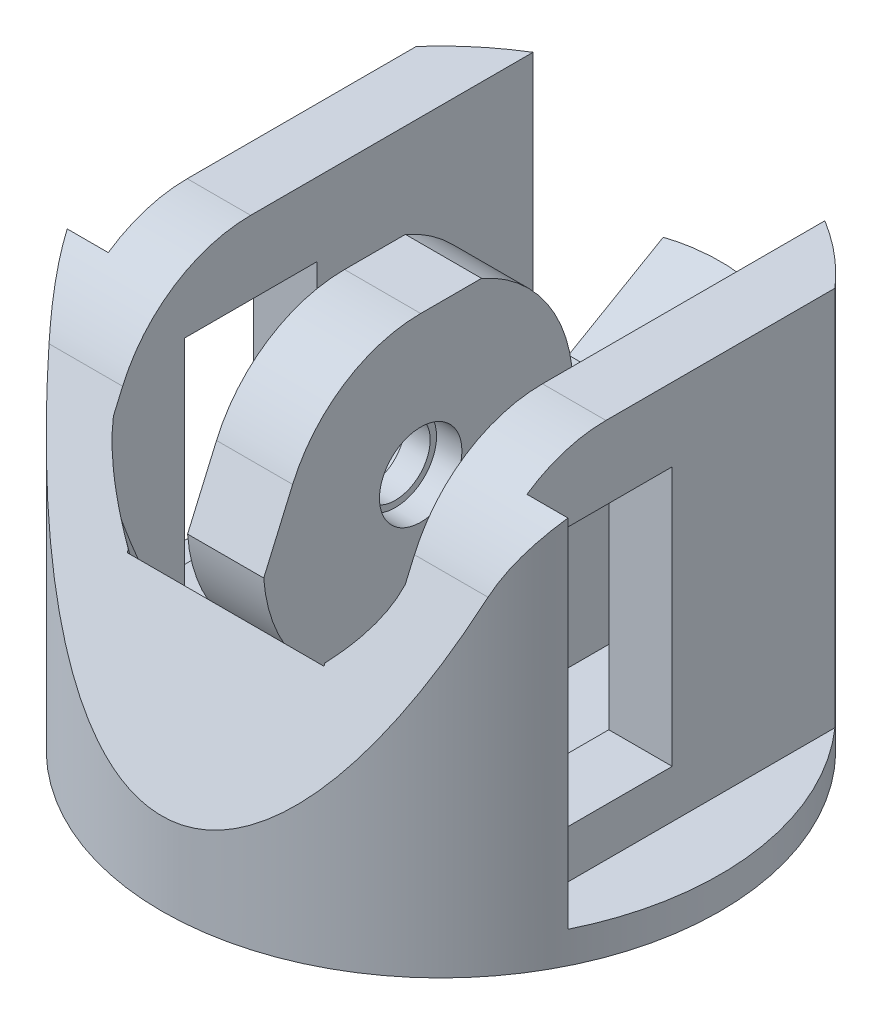
SolidWorks part; units mm, degrees
ref_plane "前视基准面" through (0, 0, 0) normal (0, 0, 1) x (1, 0, 0)
ref_plane "上视基准面" through (0, 0, 0) normal (0, 1, 0) x (1, 0, 0)
ref_plane "右视基准面" through (0, 0, 0) normal (1, 0, 0) x (0, 0, -1)
sketch "草图1" plane through (0, 0, 0) normal (0, 1, 0) x (1, 0, 0)
  circle A0 centre (0, 0) radius 44
  dimension "D1" = 88
extrude "凸台-拉伸1" add sketch "草图1" along normal blind 80
sketch "草图2" plane through (0, 0, 0) normal (0, 1, 0) x (1, 0, 0)
  line L0 (33, 29.1033) -> (33, -19.45)
  line L1 (33, -19.45) -> (39.4677, -19.45)
  line L2 (36.6, -16.45) -> (56.9, -16.45) construction
  line L3 (0, 44) -> (0, -28)
  line L4 (0, -28) -> (23, -28)
  line L5 (23, -28) -> (23, 44)
  line L6 (23, 44) -> (0, 44)
  circle A1 centre (0, 0) radius 44 construction
  arc A2 (39.4677, -19.45) -> (33, 29.1033) centre (0, 0) ccw
  dimension "D1" = 33
  dimension "D2" = 3
  dimension "D3" = 10
  dimension "D4" = 28
extrude "切除-拉伸5" cut sketch "草图2" along normal through all from offset 5
mirror "镜向1" about plane through (0, 0, 0) normal (1, 0, 0) of "切除-拉伸5"
sketch "草图3" plane through (33, 0, 0) normal (1, 0, 0) x (0, 0, -1)
  line L0 (-16.45, 52.95) -> (2.45, 52.95) construction
  line L1 (-17.45, 53.45) -> (3.45, 53.45)
  line L2 (-17.45, 53.45) -> (-17.45, 12.55)
  line L3 (-17.45, 12.55) -> (3.45, 12.55)
  line L4 (3.45, 53.45) -> (3.45, 12.55)
  line L5 (-16.95, 52.45) -> (-16.95, 13.55) construction
  line L6 (2.95, 52.45) -> (2.95, 13.55) construction
  line L7 (-16.45, 13.05) -> (2.45, 13.05) construction
  dimension "D1" = 0.5
  dimension "D2" = 0.5
  dimension "D3" = 0.5
  dimension "D4" = 0.5
extrude "切除-拉伸6" cut sketch "草图3" against normal through all
sketch "草图6" plane through (0, 5, 0) normal (0, 1, 0) x (1, 0, 0)
  line L0 (-8.2, 43.2292) -> (-8.2, -28)
  line L1 (-23, -28) -> (23, -28) construction
  line L2 (3.8, 43.8356) -> (3.8, -28)
  line L3 (-12.2, -11.2) -> (-12.2, -2.8) construction
  line L6 (-23, 37.51) -> (-23, -28)
  line L7 (-23, -28) -> (23, -28)
  line L8 (23, -28) -> (23, 37.51)
  line L10 (-8.2, -28) -> (3.8, -28)
  arc A0 (23, 37.51) -> (-23, 37.51) centre (0, 0) ccw construction
  arc A2 (23, 37.51) -> (-23, 37.51) centre (0, 0) ccw
  arc A3 (3.8, 43.8356) -> (-8.2, 43.2292) centre (0, 0) ccw
  dimension "D2" = 4
  dimension "D3" = 12
  dimension "D1" = 0
extrude "凸台-拉伸2" add sketch "草图6" along normal up to surface (75 mm away) up to face at (0, 80, 2.4377)
sketch "草图7" plane through (3.8, 0, 0) normal (1, 0, 0) x (0, 0, -1)
  circle A0 centre (-7, 43) radius 6.5
  dimension "D1" = 13
extrude "切除-拉伸7" cut sketch "草图7" against normal blind 4
sketch "草图8" plane through (-8.2, 0, 0) normal (-1, 0, 0) x (0, 0, 1)
  circle A0 centre (7, 43) radius 6.5 construction
  circle A1 centre (7, 43) radius 6.5
extrude "切除-拉伸8" cut sketch "草图8" against normal blind 4
sketch "草图9" plane through (3.8, 0, 0) normal (1, 0, 0) x (0, 0, -1)
  circle A0 centre (-7, 43) radius 5.5
  dimension "D1" = 11
extrude "切除-拉伸9" cut sketch "草图9" against normal up to next
sketch "草图10" plane through (33, 0, 0) normal (1, 0, 0) x (0, 0, -1)
  line L0 (44, 80) -> (44, 65)
  line L1 (44, 80) -> (43.2292, 80) construction
  line L2 (44, 0) -> (44, 80) construction
  line L3 (44, 65) -> (-7, 65)
  line L4 (-27.1818, 51.7576) -> (-44, 13)
  line L5 (-44, 80) -> (-44, 0) construction
  line L6 (-44, 13) -> (-44, 80)
  line L7 (-44, 80) -> (44, 80)
  arc A0 (-7, 65) -> (-27.1818, 51.7576) centre (-7, 43) ccw
  dimension "D1" = 22
  dimension "D2" = 13
extrude "切除-拉伸10" cut sketch "草图10" against normal through all both and the other way through all
ref_plane "基准面1" through (0, 43, 0) normal (0, 1, 0) x (1, 0, 0)
sketch "草图18" plane through (-8.2, 0, 0) normal (-1, 0, 0) x (0, 0, 1)
  line L0 (7, 43) -> (-13.7846, 55)
  line L1 (7, 43) -> (-28.9915, 43.7841)
  line L2 (7, 65) -> (-43.2292, 65) construction
  line L4 (7, 43) -> (7, 63.2759) construction
  line L5 (-2.5917, 65) -> (-21.4956, 65)
  circle A4 centre (7, 43) radius 24
  circle A5 centre (7, 43) radius 36
  point P3 (-2.5917, 65)
  point P9 (-21.4956, 65)
  line M9 (7, 65) -> (-43.2292, 65)
  dimension "D1" = 48
  dimension "D2" = 72
  dimension "D3" = 28.752
  dimension "D4" = 60
extrude "切除-拉伸13" cut sketch "草图18" against normal up to next contours A5 L1 A4 M9 region at (-8.2, 55.0577, -19.2929)
sketch "草图19" plane through (-8.2, 0, 0) normal (-1, 0, 0) x (0, 0, 1)
  line L0 (-13.7846, 55) -> (-25.7846, 34.2154)
  line L1 (-13.7846, 55) -> (7, 43)
  line L2 (-25.7846, 34.2154) -> (-75.1569, 62.7205)
  line L3 (7, 43) -> (7, 62.5327) construction
  line L4 (-75.1569, 62.7205) -> (-75.1569, 93.8418)
  line L5 (-75.1569, 93.8418) -> (-13.7846, 93.8418)
  line L6 (-13.7846, 93.8418) -> (-13.7846, 55)
  line M10 (-16.9943, 43.5227) -> (-28.9915, 43.7841)
  arc M11 (-28.9915, 43.7841) -> (-21.4956, 65) centre (7, 43) cw
  line M12 (-21.4956, 65) -> (-43.2292, 65)
  line M13 (-43.2292, 65) -> (-43.2292, 5)
  dimension "D1" = 24
  dimension "D2" = 24
  dimension "D3" = 60
extrude "切除-拉伸14" cut sketch "草图19" against normal up to next contours L2 L0 M10 M11 M12 M13 | L6 L5 L4 L2 L0 M13 M12 M11 M10 region at (-8.2, 73.6173, -43.7686) region at (-8.2, 51.8368, -33.5377)
sketch "草图21" plane through (-8.2, 0, 0) normal (-1, 0, 0) x (0, 0, 1)
  line L0 (44, 13) -> (27.1818, 51.7576) construction
  line L1 (34.0766, 35.8685) -> (31, 42.9586)
  line L2 (14.3622, 15.9852) -> (18.9641, 22.1947)
  circle A0 centre (7, 43) radius 24
  circle A1 centre (7, 43) radius 28
  point P6 (31, 42.9586)
  point P10 (34.0766, 35.8685)
  point P15 (7, 43)
  line M7 (28, 5) -> (28, 49.872)
  dimension "D1" = 48
  dimension "D2" = 56
  dimension "D3" = 2
extrude "切除-拉伸15" [suppressed] cut sketch "草图21" along normal up to surface and the other way up to next contours L2 A1 A0 M7 | A1 L1 A0 M7
ref_axis "基准轴1" through (-104.144, 43, 7) along (1, 0, 0)
ref_plane "基准面2" through (0, 43, 0) normal (0, -1, 0) x (-1, 0, 0)
sketch "草图24" plane through (0, 43, 0) normal (0, -1, 0) x (-1, 0, 0)
  line L0 (15.5, -31.8) -> (15.5, -34.8)
  line L1 (101.4999, -7) -> (-95.9502, -7) construction
  line L2 (104.144, -7) -> (-147.8088, -7) construction
  line L3 (-15.5, -31.8) -> (-15.5, -34.8)
  line L5 (-15.5, -34.8) -> (15.5, -34.8)
  line L6 (-23, 37.51) -> (-23, -7) construction
  line L7 (23, 37.51) -> (23, -7) construction
  line L8 (-23, 37.51) -> (-23, -7)
  line L9 (23, 37.51) -> (23, -7)
  line L10 (15.5, -31.8) -> (15.5, -7)
  line L11 (23, -34.8) -> (23, -31.8) construction
  line L14 (-23, -34.8) -> (-23, -31.8) construction
  line L15 (15.5, -7) -> (8.2, -7)
  line L16 (8.2, -7) -> (8.2, -31.8)
  line L17 (8.2, -31.8) -> (-3.8, -31.8)
  line L18 (-3.8, -31.8) -> (-3.8, -7)
  line L19 (-3.8, -7) -> (-15.5, -7)
  line L20 (-15.5, -7) -> (-15.5, -31.8)
  line L21 (15.5, -19.9764) -> (15.5, -34.5) construction
  line L22 (-3.8, -7) -> (-3.8, -27.1818) construction
  dimension "D1" = 27.8
  dimension "D2" = 7.3
  dimension "D3" = 7.5
  dimension "D4" = 7.5
  dimension "D5" = 3
revolve "切除-旋转1" cut sketch "草图24" angle 180 mid plane about L1 region at (-15.0836, 43, 33.3)
sketch "草图26" plane through (0, 43, 0) normal (0, 1, 0) x (1, 0, 0)
  line L0 (-28, -7) -> (28.2, -7) construction
  line L1 (-33, -7) -> (-23, -7) construction
  line L2 (28.2, -16.45) -> (28.2, 2.45) construction
  line L5 (-15.5, -34.5516) -> (-23, -29.3)
  line L11 (-23, -29.3) -> (-23, -28)
  line L19 (-23, -28) -> (-15.5, -28)
  line L20 (-15.5, -28) -> (-15.5, -34.5516)
  line L36 (0, -15.7401) -> (0, -38.7715) construction
  line L37 (23, -28) -> (23, 37.51) construction
  line L38 (-23, -27.1818) -> (-23, -7) construction
  line L39 (15.5, -34.5516) -> (23, -29.3)
  line L40 (15.5, -28) -> (15.5, -34.5516)
  line L41 (23, -28) -> (15.5, -28)
  line L42 (23, -29.3) -> (23, -28)
  dimension "D1" = 55
  dimension "D2" = 7.5
  dimension "D4" = 1.3
revolve "切除-旋转2" cut sketch "草图26" angle 180 mid plane about L0
sketch "草图28" plane through (3.8, 0, 0) normal (1, 0, 0) x (0, 0, -1)
  line L0 (-5.365, 18.254) -> (-6.4748, 15.205)
  line L1 (-7, 15.2) -> (-7, 18.2)
  line L2 (-7, 43) -> (-23.4736, 43) construction
  line L3 (-7, 18.2) -> (-7, 15.2) construction
  line L4 (-7, 18.2) -> (-7, 15.2)
  arc A0 (-31.7386, 41.2564) -> (-7, 18.2) centre (-7, 43) ccw construction
  arc A2 (-31.7386, 41.2564) -> (-7, 18.2) centre (-7, 43) ccw construction
  arc A6 (-28, 24.7835) -> (-7, 15.2) centre (-7, 43) ccw construction
  arc A7 (-28, 24.7835) -> (-7, 15.2) centre (-7, 43) ccw construction
  arc A8 (-7, 18.2) -> (-5.365, 18.254) centre (-7, 43) ccw
  arc A10 (-7, 15.2) -> (-6.4748, 15.205) centre (-7, 43) ccw
  point P0 (-7, 43)
  line M3 (-7, 18.2) -> (-7, 15.2)
  dimension "D2" = 70
  dimension "D3" = 3.2447
extrude "切除-拉伸20" cut sketch "草图28" against normal up to next contours A10 L0 A8 M3 region at (3.8, 16.967, 6.4131)
